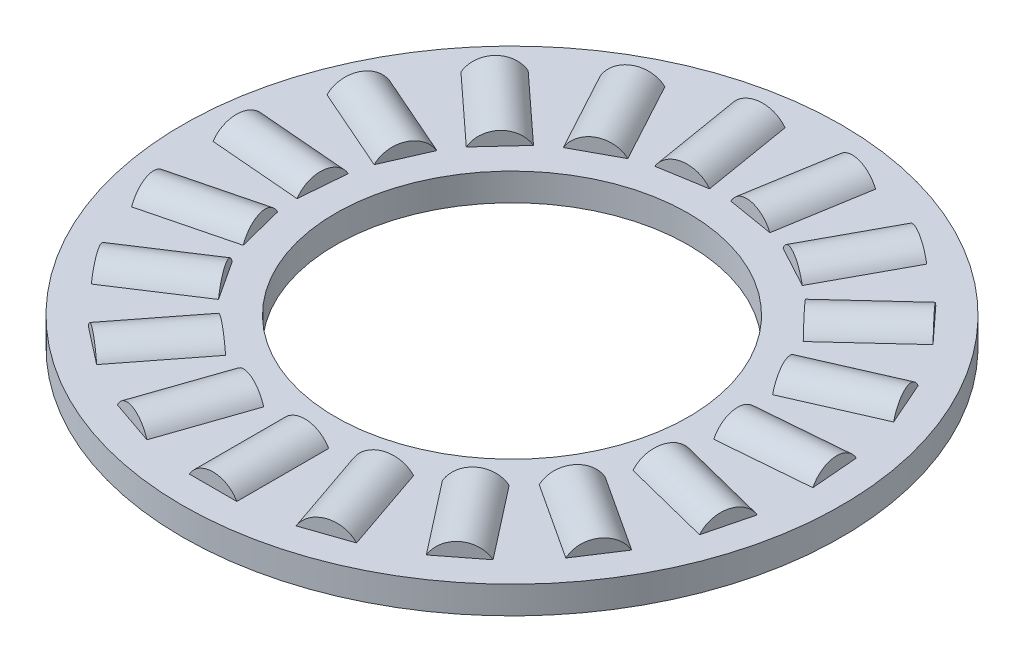
SolidWorks part; units mm, degrees
ref_plane "Front Plane" through (0, 0, 0) normal (0, 0, 1) x (1, 0, 0)
ref_plane "Top Plane" through (0, 0, 0) normal (0, 1, 0) x (1, 0, 0)
ref_plane "Right Plane" through (0, 0, 0) normal (1, 0, 0) x (0, 0, -1)
sketch "Sketch1" plane through (0, 0, 0) normal (1, 0, 0) x (0, 0, -1)
  line L0 (-11.9062, 0) -> (11.9062, 0) construction
  line L1 (0, -0.9922) -> (0, 0.9922) construction
  line L2 (-11.9062, 0.4961) -> (-6.3754, 0.4961)
  line L3 (-11.9062, 0.4961) -> (-11.9062, -0.4961)
  line L4 (-11.9062, -0.4961) -> (-6.3754, -0.4961)
  line L5 (-6.3754, 0.4961) -> (-6.3754, -0.4961)
  line L7 (-9.1408, 0.9922) -> (-9.1408, 0.4961) construction
  line L8 (-10.8001, 0.9922) -> (-7.4816, 0.9922) construction
  line L9 (-10.8001, 0.9922) -> (-10.8001, -0.9922) construction
  line L10 (-10.8001, -0.9922) -> (-7.4816, -0.9922) construction
  line L11 (-7.4816, 0.9922) -> (-7.4816, -0.9922) construction
  line L12 (11.9062, 0.9922) -> (11.9062, -0.9922) construction
  point P16 (-10.8001, 0)
  point P21 (11.9062, 0)
  dimension "OD" = 23.8125
  dimension "ID" = 12.7508
  dimension "Washer Thickness" = 0.9922
  dimension "D1" = 3.3185
  dimension "Thickness" = 1.9844
sketch "Sketch6" plane through (0, 0, 0) normal (0, 1, 0) x (1, 0, 0)
  circle A0 centre (0, 0) radius 11.9062 construction
  circle A1 centre (0, 0) radius 6.3754 construction
  circle A2 centre (0, 0) radius 6.35 construction
  dimension "For Shaft Diameter" = 12.7
  dimension "OD" = 23.8125
  dimension "ID" = 12.7508
sketch "Sketch5" plane through (0, 0, 0) normal (1, 0, 0) x (0, 0, -1)
  line L1 (-11.9062, 0.4961) -> (-6.3754, 0.4961)
  line L2 (-11.9062, 0.4961) -> (-11.9062, -0.4961)
  line L3 (-11.9062, -0.4961) -> (-6.3754, -0.4961)
  line L4 (-6.3754, 0.4961) -> (-6.3754, -0.4961)
revolve "Revolve3" add sketch "Sketch5" angle 360 about L1
sketch "Sketch3" plane through (0, 0, 0) normal (1, 0, 0) x (0, 0, -1)
  line L0 (-10.8001, 0.9922) -> (-10.8001, -0.9922) construction
  line L1 (-10.8001, 0) -> (-7.4816, 0)
  line L2 (-10.8001, 0) -> (-10.8001, 0.9922)
  line L3 (-10.8001, 0.9922) -> (-7.4816, 0.9922)
  line L4 (-7.4816, 0) -> (-7.4816, 0.9922)
revolve "Cut-Revolve1" cut sketch "Sketch3" angle 360 about L1
sketch "Sketch2" plane through (0, 0, 0) normal (1, 0, 0) x (0, 0, -1)
  line L1 (-10.8001, 0) -> (-7.4816, 0)
  line L2 (-10.8001, 0) -> (-10.8001, 0.9922)
  line L3 (-10.8001, 0.9922) -> (-7.4816, 0.9922)
  line L4 (-7.4816, 0) -> (-7.4816, 0.9922)
revolve "Revolve2" add sketch "Sketch2" angle 360 about L1
ref_axis "Axis1" through (0, 0.9922, 0) along (0, -1, 0)
pattern_circular "CirPattern1" count 19 every 18.947 about axis through (0, 0.9922, 0) along (0, -1, 0) of bodies 187 411
pattern_circular "CirPattern2" count 19 every 18.947 about axis through (0, 0.9922, 0) along (0, -1, 0) of "Cut-Revolve1"
equation "\"Rollers@CirPattern1\"= \"OD@Sketch1\" * 20"
equation "\"Angle@CirPattern1\" = 360/\"Rollers@CirPattern1\""
equation "\"D1@CirPattern2\" = \"Rollers@CirPattern1\""
equation "\"D2@CirPattern2\" = \"Angle@CirPattern1\""
equation "\"D1@Sketch1\"=((\"OD@Sketch1\"-\"ID@Sketch1\")/2)*.6"
